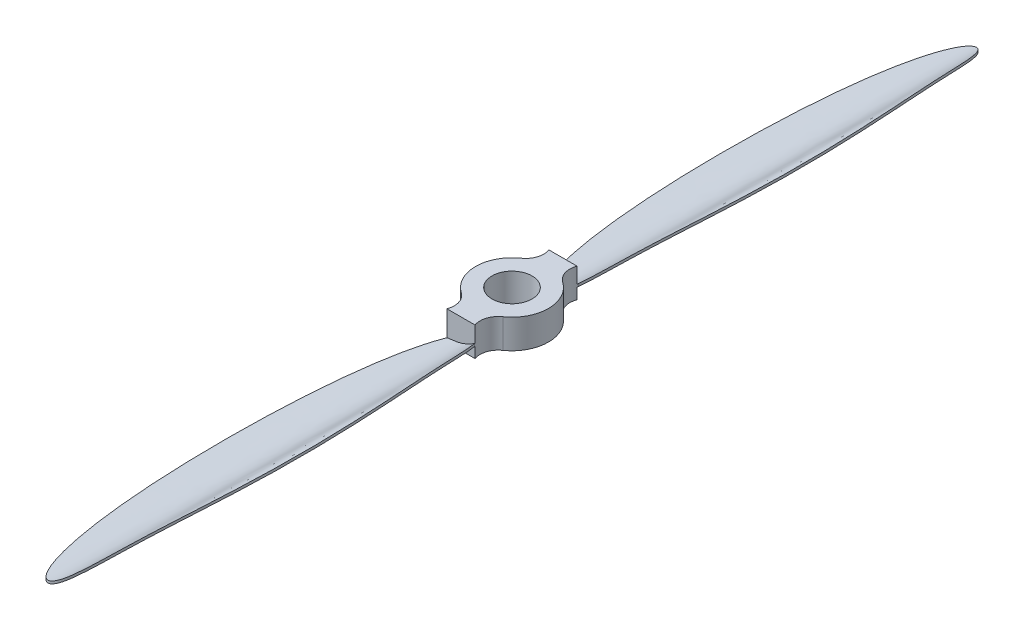
SolidWorks part; units mm, degrees
material "ABS"
ref_plane "Alzado" through (0, 0, 0) normal (0, 0, 1) x (1, 0, 0)
ref_plane "Planta" through (0, 0, 0) normal (0, 1, 0) x (1, 0, 0)
ref_plane "Vista lateral" through (0, 0, 0) normal (1, 0, 0) x (0, 0, -1)
sketch "Croquis1" plane through (0, 0, 0) normal (0, 1, 0) x (1, 0, 0)
  line L0 (0, 10) -> (0, 127) construction
  line L1 (0, -10) -> (0, -127) construction
  line L2 (-10, 0) -> (-127, 0) construction
  arc A0 (-5.705, 8.2129) -> (-5.705, -8.2129) centre (0, 0) ccw
  circle A1 centre (0, 0) radius 5.5
  circle A2 centre (0, 0) radius 127 construction
  arc A3 (-5.705, 8.2129) -> (-3.9833, 14.3385) centre (-8.5576, 12.3194) ccw
  arc A4 (5.705, 8.2129) -> (3.9833, 14.3385) centre (8.5576, 12.3194) cw
  arc A5 (5.705, -8.2129) -> (3.9833, -14.3385) centre (8.5576, -12.3194) ccw
  arc A6 (-5.705, -8.2129) -> (-3.9833, -14.3385) centre (-8.5576, -12.3194) cw
  arc A7 (5.705, -8.2129) -> (5.705, 8.2129) centre (0, 0) ccw
  ellipse E0 centre (0, 68.5) end of major axis (0, 127) minor radius 10.5402 (3.9833, 14.3385) -> (-3.9833, 14.3385) ccw
  ellipse E1 centre (0, -68.5) end of major axis (0, -127) minor radius 10.5402 (3.9833, -14.3385) -> (-3.9833, -14.3385) cw
extrude "Saliente-Extruir1" add sketch "Croquis1" along normal blind 8
ref_plane "Plano1" through (0, 0, 127) normal (0, 0, 1) x (1, 0, 0)
sketch "Croquis2" plane through (0, 0, 127) normal (0, 0, 1) x (1, 0, 0)
  line L0 (-10.5402, 0) -> (-10.5402, 0.7)
  line L1 (-10.5402, 8) -> (-10.5402, 0) construction
  line L2 (10.5402, 7.3) -> (10.5402, 8)
  line L3 (-10.5402, 0.7) -> (-10.5402, 8)
  line L4 (-10.5402, 8) -> (10.5402, 8)
  line L5 (10.5402, 7.3) -> (10.5402, 0)
  line L6 (10.5402, 0) -> (-10.5402, 0)
  line L7 (-12.847, 0) -> (-12.847, 4.5585) construction
  line L8 (-36.2342, 0) -> (-15.1539, 0)
  line L9 (-36.2342, 7.3) -> (-36.2342, 0)
  line L10 (-15.1539, 8) -> (-36.2342, 8)
  line L11 (-15.1539, 0.7) -> (-15.1539, 8)
  line L12 (-36.2342, 7.3) -> (-36.2342, 8)
  line L13 (-15.1539, 0) -> (-15.1539, 0.7)
  spline S0 degree 3 poles (-10.5402, 0.7) (-6.6035, 1.1648) (0.425, 0.4785) (6.2362, 5.6452) (8.9141, 7.8975) (10.5402, 8) knots 0 0 0 0 0.556269 0.795859 1 1 1 1
  spline S1 degree 3 poles (-10.5402, 0) (-6.6035, 0.4648) (0.425, -0.2215) (6.2362, 4.9452) (8.9141, 7.1975) (10.5402, 7.3) knots 0 0 0 0 0.556269 0.795859 1 1 1 1
  spline S2 degree 3 poles (-15.1539, 0) (-19.0905, 0.4648) (-26.119, -0.2215) (-31.9303, 4.9452) (-34.6082, 7.1975) (-36.2342, 7.3) knots 0 0 0 0 0.556269 0.795859 1 1 1 1
  spline S3 degree 3 poles (-15.1539, 0.7) (-19.0905, 1.1648) (-26.119, 0.4785) (-31.9303, 5.6452) (-34.6082, 7.8975) (-36.2342, 8) knots 0 0 0 0 0.556269 0.795859 1 1 1 1
extrude "Cortar-Extruir1" cut sketch "Croquis2" against normal blind 113 contours L3 S0 L4 | S1 L6 L5 region at (5.9137, 2.4194, 127) region at (-2.7074, 4.9134, 127)
ref_plane "Plano2" through (0, 0, -127) normal (0, 0, -1) x (-1, 0, 0)
sketch "Croquis3" plane through (0, 0, -127) normal (0, 0, -1) x (-1, 0, 0)
  line L1 (-10.5402, 0) -> (10.5402, 0)
  line L2 (-10.5402, 7.3) -> (-10.5402, 0)
  line L3 (10.5402, 8) -> (-10.5402, 8)
  line L4 (10.5402, 0.7) -> (10.5402, 8)
  line L5 (-10.5402, 7.3) -> (-10.5402, 8)
  line L6 (10.5402, 0) -> (10.5402, 0.7)
  spline S0 degree 3 poles (10.5402, 0) (6.6035, 0.4648) (-0.425, -0.2215) (-6.2362, 4.9452) (-8.9141, 7.1975) (-10.5402, 7.3) knots 0 0 0 0 0.556269 0.795859 1 1 1 1
  spline S1 degree 3 poles (10.5402, 0.7) (6.6035, 1.1648) (-0.425, 0.4785) (-6.2362, 5.6452) (-8.9141, 7.8975) (-10.5402, 8) knots 0 0 0 0 0.556269 0.795859 1 1 1 1
  point P0 (10.5402, 0)
extrude "Cortar-Extruir2" cut sketch "Croquis3" against normal blind 113 contours L1 S0 L2 | S1 L4 L3 region at (5.9152, 2.4195, -127) region at (-2.7071, 4.9131, -127)
